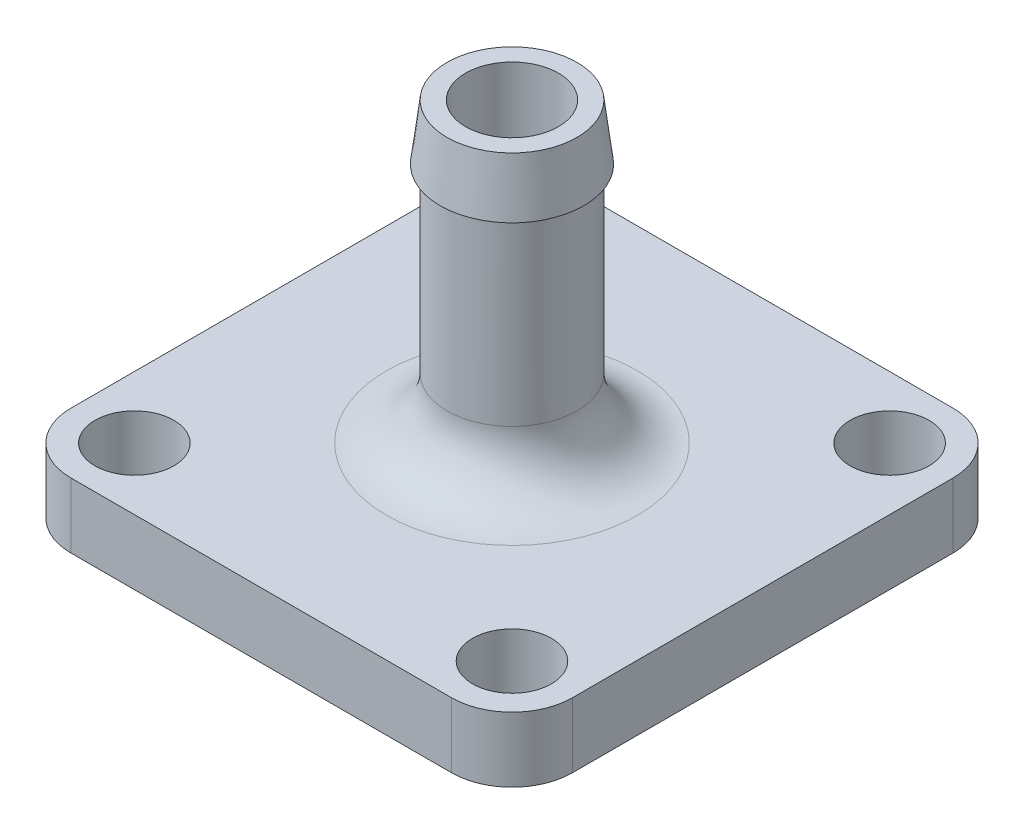
SolidWorks part; units mm, degrees
ref_plane "Front Plane" through (0, 0, 0) normal (0, 0, 1) x (1, 0, 0)
ref_plane "Top Plane" through (0, 0, 0) normal (0, 1, 0) x (1, 0, 0)
ref_plane "Right Plane" through (0, 0, 0) normal (1, 0, 0) x (0, 0, -1)
sketch "Sketch1" plane through (0, 0, 0) normal (0, 1, 0) x (1, 0, 0)
  line L0 (0, 27) -> (0, -27) construction
  line L1 (-27, 27) -> (27, 27)
  line L2 (-27, 27) -> (-27, -27)
  line L3 (-27, -27) -> (27, -27)
  line L4 (27, 27) -> (27, -27)
  line L5 (-27, 27) -> (27, -27) construction
  line L6 (-27, -27) -> (27, 27) construction
  line L7 (-17.3241, 17.3241) -> (17.3241, 17.3241) construction
  line L8 (-17.3241, 17.3241) -> (-17.3241, -17.3241) construction
  line L9 (-17.3241, -17.3241) -> (17.3241, -17.3241) construction
  line L10 (17.3241, 17.3241) -> (17.3241, -17.3241) construction
  line L11 (-17.3241, 17.3241) -> (17.3241, -17.3241) construction
  line L12 (-17.3241, -17.3241) -> (17.3241, 17.3241) construction
  circle A0 centre (-20.3293, 20.3293) radius 4.25
  circle A1 centre (20.3293, -20.3293) radius 4.25
  circle A2 centre (-20.3293, -20.3293) radius 4.25
  circle A3 centre (20.3293, 20.3293) radius 4.25
  point P0 (0, 0)
  point P6 (0, 0)
  dimension "D4" = 8.5
  dimension "D1" = 54
  dimension "D2" = 54
  dimension "D3" = 49
extrude "Boss-Extrude1" add sketch "Sketch1" along normal blind 7
fillet "Fillet2" radius 6.5 4 edges at (-27, 3.5, 27) (27, 3.5, 27) (27, 3.5, -27) (-27, 3.5, -27)
sketch "Sketch4" plane through (0, 7, 0) normal (0, 1, 0) x (1, 0, 0)
  circle A0 centre (0, 0) radius 7
  dimension "D1" = 14
extrude "Boss-Extrude3" add sketch "Sketch4" along normal blind 26
sketch "Sketch5" plane through (0, 33, 0) normal (0, 1, 0) x (1, 0, 0)
  circle A0 centre (0, 0) radius 7.75
  dimension "D1" = 15.5
extrude "Boss-Extrude4" add sketch "Sketch5" along normal blind 6
ref_plane "Plane1" through (0, 0, 0) normal (0, 0, 1) x (1, 0, 0)
sketch "Sketch6" plane through (0, 0, 0) normal (0, 0, 1) x (1, 0, 0)
  line L0 (0, 39) -> (0, 0) construction
  line L1 (7.75, 39) -> (-7.75, 39) construction
  line L2 (7, 33) -> (7, 39) construction
  line L3 (-7.75, 33) -> (7.75, 33) construction
  line L4 (-7, 33) -> (7, 33) construction
  line L5 (6.8959, 39.847) -> (7.9357, 31.389)
  line L6 (6.8959, 39.847) -> (8.5146, 39.847)
  line L7 (8.5146, 39.847) -> (8.5146, 31.389)
  line L8 (8.5146, 31.389) -> (7.9357, 31.389)
  dimension "D1" = 7
revolve "Cut-Revolve1" cut sketch "Sketch6" angle 360 about L0
fillet "Fillet3" radius 6.5 1 edges at (0, 7, 7)
ref_plane "Plane2" through (0, 0, 0) normal (0, 0, 1) x (1, 0, 0)
sketch "Sketch7" plane through (0, 0, 0) normal (0, 0, 1) x (1, 0, 0)
  line L0 (0, 39) -> (0, 0) construction
  line L1 (7, 39) -> (-7, 39) construction
  line L2 (5, 41.6737) -> (5, 5)
  line L3 (0, 39) -> (7, 39) construction
  line L4 (-27, 5) -> (27, 5) construction
  line L5 (-27, 7) -> (-27, 0) construction
  line L6 (27, 0) -> (27, 7) construction
  line L7 (27, 7) -> (20.5, 7) construction
  line L8 (14.5, 5) -> (14.5, 0)
  line L9 (20.5, 0) -> (-20.5, 0) construction
  line L10 (14.5, 5) -> (5, 5)
  line L11 (5, 41.6737) -> (0, 41.6737)
  line L12 (0, 41.6737) -> (0, -2.1097)
  line L13 (0, -2.1097) -> (14.5, 0)
  point P20 (14.5, 2.5)
  dimension "D1" = 2
  dimension "D2" = 2
  dimension "D3" = 14.5
revolve "Cut-Revolve2" cut sketch "Sketch7" angle 360 about L12
fillet "Fillet4" radius 6.5 1 edges at (-5, 5, 0)
fillet "Fillet5" radius 6.5 1 edges at (-14.5, 5, 0)
